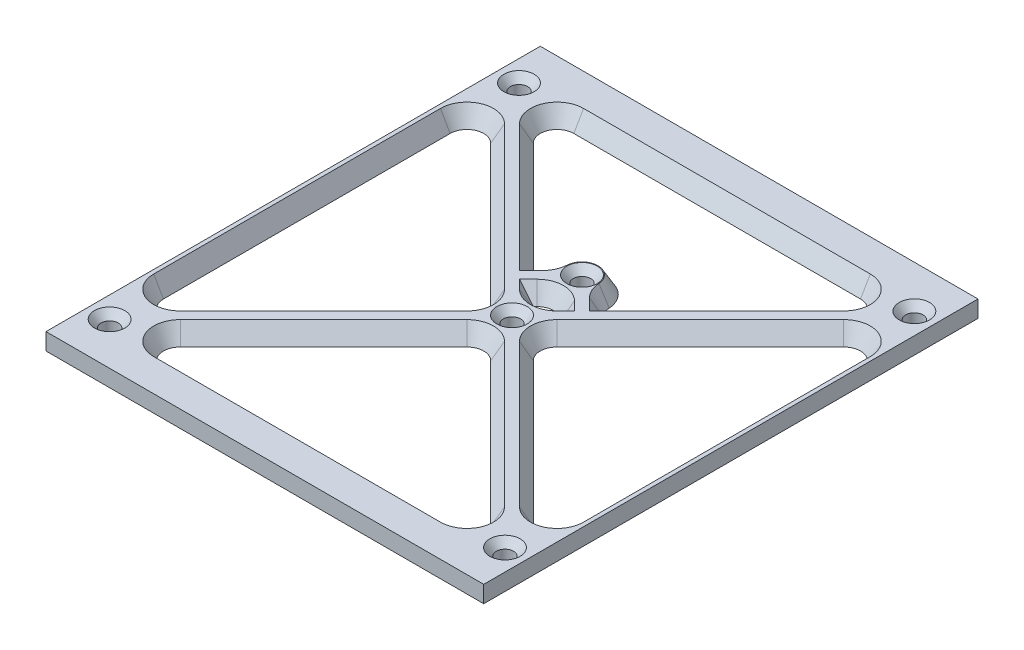
SolidWorks part; units mm, degrees
material "ABS"
ref_plane "Front Plane" through (0, 0, 0) normal (0, 0, 1) x (1, 0, 0)
ref_plane "Top Plane" through (0, 0, 0) normal (0, 1, 0) x (1, 0, 0)
ref_plane "Right Plane" through (0, 0, 0) normal (1, 0, 0) x (0, 0, -1)
sketch "Sketch1" plane through (0, 0, 0) normal (0, 1, 0) x (1, 0, 0)
  line L1 (-41.5, -46.825) -> (41.5, -46.825)
  line L2 (-41.5, -46.825) -> (-41.5, 46.825)
  line L3 (-41.5, 46.825) -> (41.5, 46.825)
  line L4 (41.5, -46.825) -> (41.5, 46.825)
  line L5 (-41.5, -46.825) -> (41.5, 46.825) construction
  line L6 (-41.5, 46.825) -> (41.5, -46.825) construction
  point P0 (0, 0)
  dimension "D1" = 83
  dimension "D2" = 93.65
extrude "Boss-Extrude1" add sketch "Sketch1" along normal blind 3.175
hole_wizard "CSK for #4 Flat Head Machine Screw1" positions "Sketch3" profile "Sketch2" countersink size "#4" standard "ANSI Inch" end condition through all
sketch "Sketch3" plane through (0, 3.175, 0) normal (0, 1, 0) x (1, 0, 0)
  circle A0 centre (37.25, 38.575) radius 1.4732 construction
  circle A1 centre (37.25, -38.575) radius 1.4732 construction
  circle A2 centre (-37.25, 38.575) radius 1.4732 construction
  circle A3 centre (-37.25, -38.575) radius 1.4732 construction
  point P0 (37.25, 38.575)
  point P2 (37.25, -38.575)
  point P4 (-37.25, -38.575)
  point P6 (-37.25, 38.575)
sketch "Sketch2" plane through (37.25, 3.175, -38.575) normal (1, 0, 0) x (0, 0, 1)
  line L0 (0, 0) -> (0, 3.175)
  line L1 (0, 3.175) -> (1.6319, 3.175)
  line L2 (1.6319, 3.175) -> (1.6319, 1.4098)
  line L3 (1.6319, 1.4098) -> (2.8575, 0)
  line L5 (2.8575, 0) -> (0, 0)
  line L6 (-1.632, 1.4098) -> (-2.8575, 0) construction
  line L11 (0, -6.35) -> (0, 107.95) construction
  dimension "Thru Hole Dia." = 3.2639
  dimension "Thru Hole Depth" = 3.175
  dimension "Near C'Sink Dia." = 5.715
  dimension "Near C'Sink Angle" = 82
sketch "Sketch4" plane through (0, 3.175, 0) normal (0, 1, 0) x (1, 0, 0)
  line L0 (-40.5, 27.0147) -> (-40.5, -27.0147)
  line L1 (-27.0147, -40.5) -> (27.0147, -40.5)
  line L2 (40.5, -27.0147) -> (40.5, 27.0147)
  line L3 (-27.0147, 40.5) -> (27.0147, 40.5)
  line L6 (-35.5, -35.5) -> (35.5, 35.5) construction
  line L7 (35.5, -35.5) -> (-35.5, 35.5) construction
  line L8 (-30.5503, -31.9645) -> (-3.5355, -4.9497)
  line L9 (30.5503, -31.9645) -> (3.5355, -4.9497)
  line L10 (-31.9645, -30.5503) -> (-4.9497, -3.5355)
  line L11 (31.9645, -30.5503) -> (4.9497, -3.5355)
  line L12 (4.9497, 3.5355) -> (31.9645, 30.5503)
  line L13 (-4.9497, 3.5355) -> (-31.9645, 30.5503)
  line L14 (-3.5355, 4.9497) -> (-30.5503, 31.9645)
  line L15 (3.5355, 4.9497) -> (30.5503, 31.9645)
  line L16 (-41.5, 46.825) -> (-41.5, -46.825) construction
  line L17 (-35.5, -35.5) -> (35.5, -35.5) construction
  line L18 (-35.5, -35.5) -> (-35.5, 35.5) construction
  line L19 (-35.5, 35.5) -> (35.5, 35.5) construction
  line L20 (35.5, -35.5) -> (35.5, 35.5) construction
  arc A0 (-30.5503, -31.9645) -> (-27.0147, -40.5) centre (-27.0147, -35.5) ccw
  arc A1 (-31.9645, -30.5503) -> (-40.5, -27.0147) centre (-35.5, -27.0147) cw
  arc A2 (-40.5, 27.0147) -> (-31.9645, 30.5503) centre (-35.5, 27.0147) cw
  arc A3 (-27.0147, 40.5) -> (-30.5503, 31.9645) centre (-27.0147, 35.5) ccw
  arc A4 (40.5, 27.0147) -> (31.9645, 30.5503) centre (35.5, 27.0147) ccw
  arc A5 (27.0147, 40.5) -> (30.5503, 31.9645) centre (27.0147, 35.5) cw
  arc A6 (-3.5355, 4.9497) -> (3.5355, 4.9497) centre (0, 8.4853) ccw
  arc A7 (-4.9497, 3.5355) -> (-4.9497, -3.5355) centre (-8.4853, 0) cw
  arc A8 (-3.5355, -4.9497) -> (3.5355, -4.9497) centre (0, -8.4853) cw
  arc A9 (4.9497, 3.5355) -> (4.9497, -3.5355) centre (8.4853, 0) ccw
  arc A10 (31.9645, -30.5503) -> (40.5, -27.0147) centre (35.5, -27.0147) ccw
  arc A11 (30.5503, -31.9645) -> (27.0147, -40.5) centre (27.0147, -35.5) cw
  point P2 (0, 0)
  dimension "D1" = 5
  dimension "D2" = 1
  dimension "D4" = 2
  dimension "D5" = 2
extrude "Cut-Extrude1" cut sketch "Sketch4" against normal through all draft 30
hole_wizard "CSK for #4 Flat Head Machine Screw2" positions "Sketch6" profile "Sketch5" countersink size "#4" standard "ANSI Inch" end condition through all
sketch "Sketch6" plane through (0, 3.175, 0) normal (0, 1, 0) x (1, 0, 0)
  point P0 (0, 0)
sketch "Sketch5" plane through (0, 3.175, 0) normal (1, 0, 0) x (0, 0, 1)
  line L0 (0, 0) -> (0, 3.175)
  line L1 (0, 3.175) -> (1.6319, 3.175)
  line L2 (1.6319, 3.175) -> (1.6319, 1.4098)
  line L3 (1.6319, 1.4098) -> (2.8575, 0)
  line L5 (2.8575, 0) -> (0, 0)
  line L6 (-1.6319, 1.4098) -> (-2.8575, 0) construction
  line L11 (0, -6.35) -> (0, 107.95) construction
  dimension "Thru Hole Dia." = 3.2639
  dimension "Thru Hole Depth" = 3.175
  dimension "Near C'Sink Dia." = 5.715
  dimension "Near C'Sink Angle" = 82
sketch "Sketch7" plane through (0, 3.175, 0) normal (0, 1, 0) x (1, 0, 0)
  line L0 (41.246, -46.571) -> (41.246, 46.571)
  line L1 (41.246, 46.571) -> (-41.246, 46.571)
  line L2 (-41.246, 46.571) -> (-41.246, -46.571)
  line L3 (-41.246, -46.571) -> (41.246, -46.571)
  line L4 (41.5, -46.825) -> (41.5, 46.825)
  line L5 (41.5, 46.825) -> (-41.5, 46.825)
  line L6 (-41.5, 46.825) -> (-41.5, -46.825)
  line L7 (-41.5, -46.825) -> (41.5, -46.825)
  line L8 (41.5, -46.825) -> (41.5, 46.825)
  line L9 (41.5, 46.825) -> (-41.5, 46.825)
  line L10 (-41.5, 46.825) -> (-41.5, -46.825)
  line L11 (-41.5, -46.825) -> (41.5, -46.825)
  dimension "D1" = 0
  dimension "D2" = 0.254
extrude "Cut-Extrude2" cut sketch "Sketch7" against normal through all
ref_axis "Axis1" through (0, 0, 0) along (0, 1, 0)
sketch "Sketch8" plane through (0, 3.175, 0) normal (0, 1, 0) x (1, 0, 0)
  line L0 (0, 0) -> (0, 40.5) construction
  line L1 (27.0147, 40.5) -> (-27.0147, 40.5) construction
  line L2 (-5.8879, 7.3021) -> (0, 13.19) construction
  line L3 (-30.5503, 31.9645) -> (-3.5355, 4.9497) construction
  line L4 (0, 13.19) -> (5.8879, 7.3021) construction
  line L5 (3.5355, 4.9497) -> (30.5503, 31.9645) construction
  line L6 (-6.595, 8.0092) -> (-4.4488, 10.1554)
  line L7 (4.4488, 10.1554) -> (6.595, 8.0092)
  line L8 (-5.1808, 6.595) -> (-3.5355, 8.2403)
  line L9 (3.5355, 8.2403) -> (5.1808, 6.595)
  line L11 (-3.5355, 4.9497) -> (-4.9497, 3.5355) construction
  line L12 (-6.595, 8.0092) -> (-5.1808, 6.595)
  line L16 (6.595, 8.0092) -> (5.1808, 6.595)
  arc A0 (-3.5355, 4.9497) -> (3.5355, 4.9497) centre (0, 8.4853) ccw construction
  arc A1 (-1, 3.5863) -> (1, 3.5863) centre (0, 8.4853) ccw
  arc A2 (2.9941, 13.3779) -> (-2.9941, 13.3779) centre (0, 13.19) ccw
  arc A3 (2.9941, 13.3779) -> (4.4488, 10.1554) centre (7.9843, 13.691) ccw
  arc A4 (-3.5355, 8.2403) -> (3.5355, 8.2403) centre (0, 4.7047) cw
  arc A5 (-2.9941, 13.3779) -> (-4.4488, 10.1554) centre (-7.9843, 13.691) cw
  line M31 (-3.5355, 4.9497) -> (-30.5503, 31.9645)
  line M33 (-27.0147, 40.5) -> (27.0147, 40.5)
  line M35 (30.5503, 31.9645) -> (3.5355, 4.9497)
  dimension "D1" = 5
  dimension "D3" = 6
  dimension "D4" = 5
  dimension "D2" = 13.19
extrude "Boss-Extrude2" add sketch "Sketch8" against normal through all draft 30 contours L8 A4 L9 L7 L6 M35 M33 M31 region at (0, 3.175, -11.3776) draft outward yes
hole_wizard "CSK for #4 Flat Head Machine Screw3" positions "Sketch10" profile "Sketch9" countersink size "#4" standard "ANSI Inch" end condition through all
sketch "Sketch10" plane through (0, 3.175, 0) normal (0, 1, 0) x (1, 0, 0)
  point P0 (0, 13.19)
  dimension "D1" = 13.19
sketch "Sketch9" plane through (0, 3.175, -13.19) normal (1, 0, 0) x (0, 0, 1)
  line L0 (0, 0) -> (0, 3.175)
  line L1 (0, 3.175) -> (1.6319, 3.175)
  line L2 (1.6319, 3.175) -> (1.6319, 1.4098)
  line L3 (1.6319, 1.4098) -> (2.8575, 0)
  line L5 (2.8575, 0) -> (0, 0)
  line L6 (-1.6319, 1.4098) -> (-2.8575, 0) construction
  line L11 (0, -6.35) -> (0, 107.95) construction
  dimension "Thru Hole Dia." = 3.2639
  dimension "Thru Hole Depth" = 3.175
  dimension "Near C'Sink Dia." = 5.715
  dimension "Near C'Sink Angle" = 82
